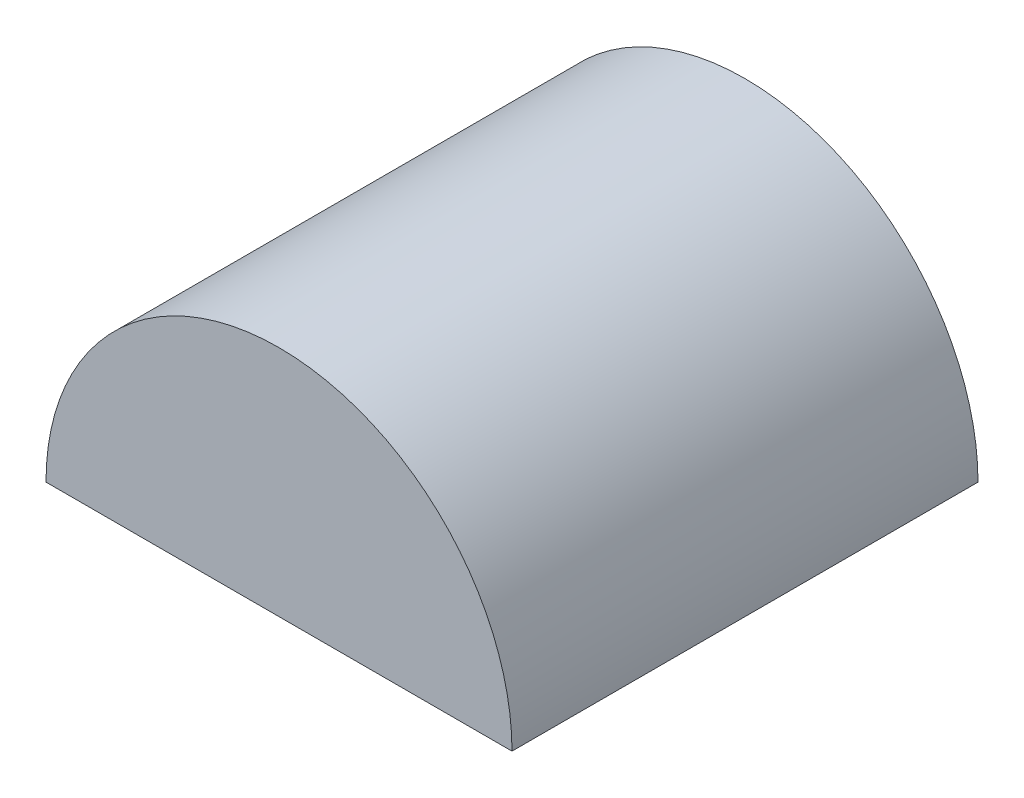
SolidWorks part; units mm, degrees
ref_plane "Front Plane" through (0, 0, 0) normal (0, 0, 1) x (1, 0, 0)
ref_plane "Top Plane" through (0, 0, 0) normal (0, 1, 0) x (1, 0, 0)
ref_plane "Right Plane" through (0, 0, 0) normal (1, 0, 0) x (0, 0, -1)
sketch "Sketch1" plane through (0, 0, 0) normal (0, 0, 1) x (1, 0, 0)
  line L0 (0, 0) -> (-0.25, 0)
  line L1 (0, 0) -> (0.25, 0)
  arc A0 (-0.25, 0) -> (0.25, 0) centre (0, 0) cw
  dimension "D1" = 0.25
extrude "Boss-Extrude1" add sketch "Sketch1" along normal blind 0.5
equation "\"t\"= 0.25'thickness of the sheets"
equation "\"t_cf\"= 0.115'thickness of single carbon fiber layer"
equation "\"t_kapton\"= 0.025'thickness of single Kapton flex layer"
equation "\"t_fr4\"= 0.1'thickness of FR4 with copper layer"
equation "\"joint_flex\"= 0.1'Width of flextures gap"
equation "\"joint_flex_eff\"= 0.02'Width of flecture after castelation"
equation "\"joint_fold\"= 0.2'Width of folding joints for 90deg fold"
equation "\"gap_tolerance\"= 0.002'Width to have interfecence fit between carbon fiber inserts"
equation "\"assemble_angle\"= 90'Angle of assembly parts"
equation "\"link_lift\"= 0.5'Actuation linkage amplification for the lift motion"
equation "\"link_swing\"= 0.45'Actuation linkage amplification for the swing motion"
equation "\"D1@Boss-Extrude1\"=\"joint_fold\""
equation "\"D1@Sketch1\"=\"t\""
